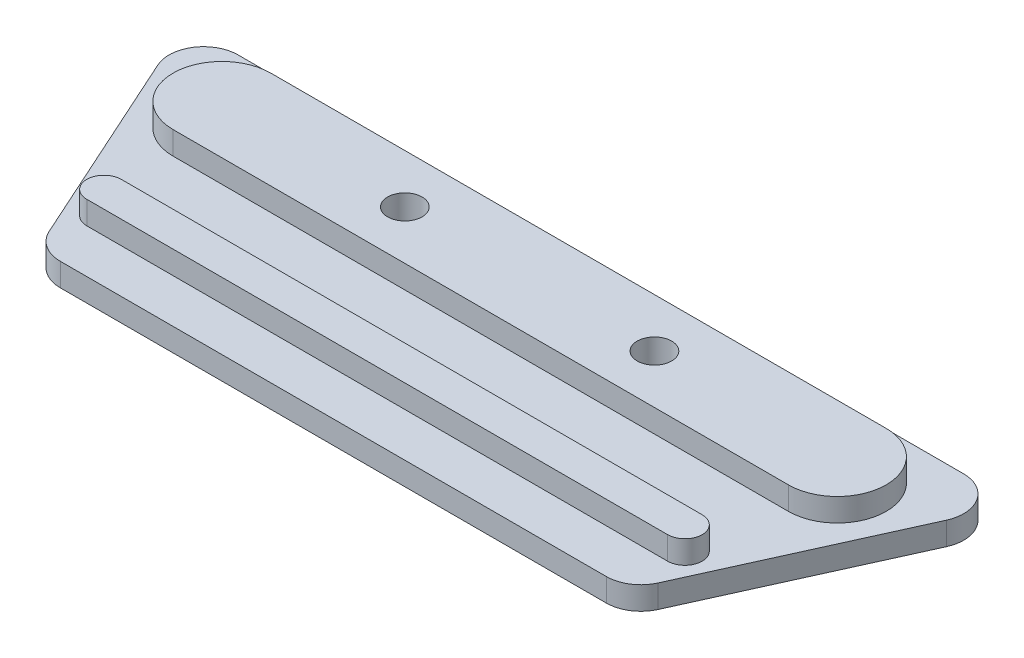
SolidWorks part; units mm, degrees
ref_plane "前视基准面" through (0, 0, 0) normal (0, 0, 1) x (1, 0, 0)
ref_plane "上视基准面" through (0, 0, 0) normal (0, 1, 0) x (1, 0, 0)
ref_plane "右视基准面" through (0, 0, 0) normal (1, 0, 0) x (0, 0, -1)
sketch "草图1" plane through (0, 0, 0) normal (0, 1, 0) x (1, 0, 0)
  line L0 (-26.75, 16) -> (26.75, 16)
  line L1 (-25.25, -1.5) -> (26.75, -1.5)
  line L3 (-25.25, 1.5) -> (25.25, 1.5)
  line L5 (-26.75, -1.5) -> (26.75, 1.5) construction
  line L6 (-26.75, 1.5) -> (26.75, -1.5) construction
  line L7 (-31, 11.75) -> (-31, 7.5)
  line L9 (-31, 7.5) -> (31, 7.5)
  line L10 (-31, 16) -> (31, 7.5) construction
  line L11 (31, 16) -> (-31, 7.5) construction
  line L12 (23.7358, -5.3188) -> (-23.7358, -5.3188)
  line L13 (-26.4693, -3.555) -> (-34.2779, 13.7109)
  line L14 (-31.5445, 17.9471) -> (31.5445, 17.9471)
  line L15 (0, 17.9471) -> (0, 16) construction
  line L16 (26.4693, -3.555) -> (34.2779, 13.7109)
  arc A0 (-25.6716, 1.4395) -> (-25.25, 1.5) centre (-25.25, 0) cw
  arc A1 (25.25, 1.5) -> (25.6716, 1.4395) centre (25.25, 0) cw
  arc A2 (-25.25, 1.5) -> (-25.25, -1.5) centre (-25.25, 0) ccw
  arc A3 (25.25, -1.5) -> (25.25, 1.5) centre (25.25, 0) ccw
  arc A4 (-26.75, 16) -> (-26.75, 7.5) centre (-26.75, 11.75) ccw
  arc A5 (26.75, 7.5) -> (26.75, 16) centre (26.75, 11.75) ccw
  arc A6 (-23.7358, -5.3188) -> (-26.4693, -3.555) centre (-23.7358, -2.3188) cw
  arc A7 (-34.2779, 13.7109) -> (-31.5445, 17.9471) centre (-31.5445, 14.9471) cw
  arc A8 (23.7358, -5.3188) -> (26.4693, -3.555) centre (23.7358, -2.3188) ccw
  arc A9 (34.2779, 13.7109) -> (31.5445, 17.9471) centre (31.5445, 14.9471) ccw
  circle A10 centre (-10.85, 11.75) radius 1.5
  circle A11 centre (10.85, 11.75) radius 1.5
  point P0 (0, 0)
  point P14 (0, 7.5)
  point P15 (0, 11.75)
  point P16 (0, 1.5)
  point P38 (0, -5.3188)
  dimension "D3" = 1.5
  dimension "D4" = 1.5
  dimension "D9" = 3
  dimension "D10" = 3
  dimension "D1" = 53.5
  dimension "D2" = 3
  dimension "D5" = 62
  dimension "D6" = 8.5
  dimension "D7" = 6
  dimension "D8" = 4.25
  dimension "D11" = 10.85
extrude "凸台-拉伸1" add sketch "草图1" along normal blind 2 contours L16 A9 L14 A7 L13 A6 L12 A8 A3 L1 A2 A0 L3 A1 A5 L9 L7 A4 L0 | L9 A5 L0 A4 A10 A11 | A4 L7 L9 | L1 A3 A1 L3 A0 A2 region at (0, 0, -11.75) region at (-30.0507, 0, -8.4493) region at (0, 0, 0) region at (0.1545, 0, -5.0823)
sketch "草图2" plane through (0, 2, 0) normal (0, 1, 0) x (1, 0, 0)
  line L4 (26.4693, -3.555) -> (34.2779, 13.7109)
  line L5 (31.5445, 17.9471) -> (-31.5445, 17.9471)
  line L6 (-34.2779, 13.7109) -> (-26.4693, -3.555)
  line L7 (-23.7358, -5.3188) -> (23.7358, -5.3188)
  line L8 (26.4693, -3.555) -> (34.2779, 13.7109)
  line L9 (31.5445, 17.9471) -> (-31.5445, 17.9471)
  line L10 (-34.2779, 13.7109) -> (-26.4693, -3.555)
  line L11 (-23.7358, -5.3188) -> (23.7358, -5.3188)
  arc A4 (34.2779, 13.7109) -> (31.5445, 17.9471) centre (31.5445, 14.9471) ccw
  arc A5 (-31.5445, 17.9471) -> (-34.2779, 13.7109) centre (-31.5445, 14.9471) ccw
  arc A6 (-26.4693, -3.555) -> (-23.7358, -5.3188) centre (-23.7358, -2.3188) ccw
  arc A7 (23.7358, -5.3188) -> (26.4693, -3.555) centre (23.7358, -2.3188) ccw
  arc A8 (34.2779, 13.7109) -> (31.5445, 17.9471) centre (31.5445, 14.9471) ccw
  arc A9 (-31.5445, 17.9471) -> (-34.2779, 13.7109) centre (-31.5445, 14.9471) ccw
  arc A10 (-26.4693, -3.555) -> (-23.7358, -5.3188) centre (-23.7358, -2.3188) ccw
  arc A11 (23.7358, -5.3188) -> (26.4693, -3.555) centre (23.7358, -2.3188) ccw
  dimension "D1" = 0
extrude "凸台-拉伸2" add sketch "草图1<3>" along normal blind 4 contours L9 A5 L0 A4 A10 A11 | L1 A3 A1 L3 A0 A2 region at (0, 0, -11.75) region at (0, 0, 0)
sketch "草图1<3>" plane through (0, 0, 0) normal (0, 1, 0) x (1, 0, 0) same geometry as "草图1"
